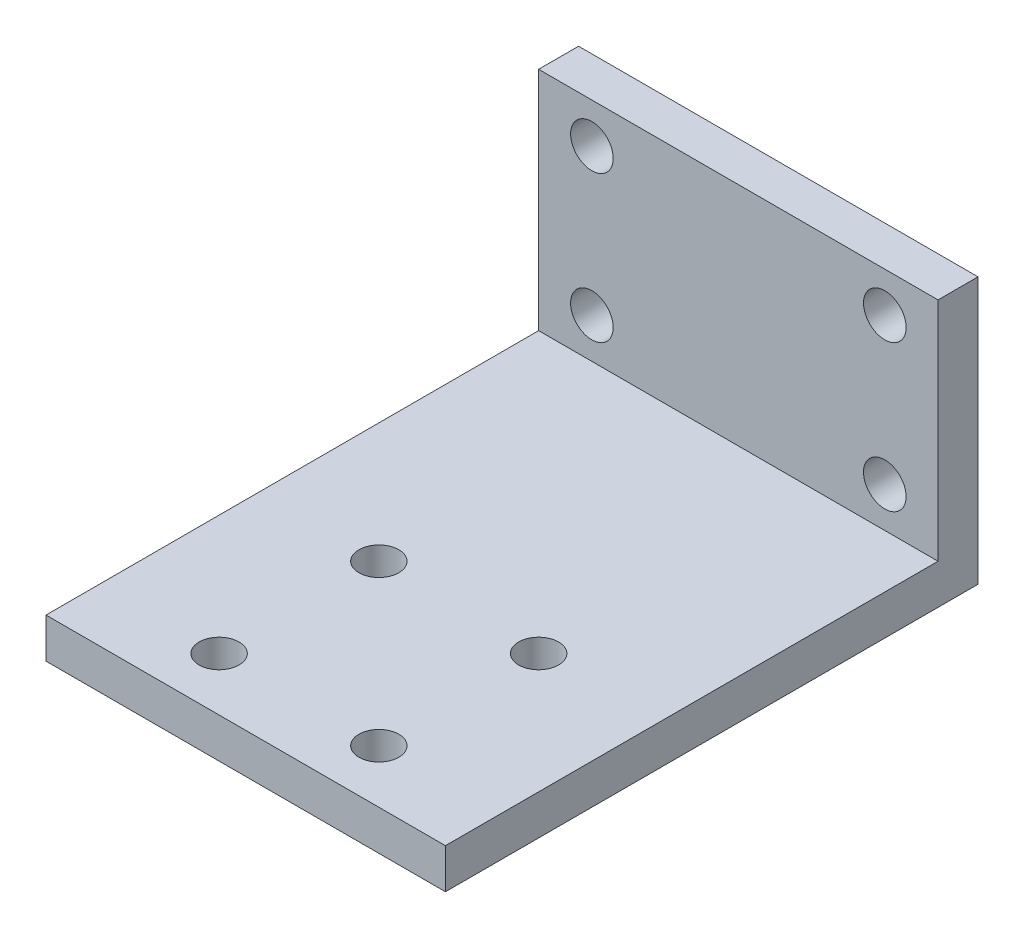
SolidWorks part; units mm, degrees
ref_plane "前视基准面" through (0, 0, 0) normal (0, 0, 1) x (1, 0, 0)
ref_plane "上视基准面" through (0, 0, 0) normal (0, 1, 0) x (1, 0, 0)
ref_plane "右视基准面" through (0, 0, 0) normal (1, 0, 0) x (0, 0, -1)
sketch "草图1" plane through (0, 0, 0) normal (0, 1, 0) x (1, 0, 0)
  line L1 (-21.3353, 6.9139) -> (8.6647, 6.9139)
  line L2 (-21.3353, 6.9139) -> (-21.3353, -33.0861)
  line L3 (-21.3353, -33.0861) -> (8.6647, -33.0861)
  line L4 (8.6647, 6.9139) -> (8.6647, -33.0861)
  dimension "D1" = 30
  dimension "D2" = 40
extrude "凸台-拉伸1" add sketch "草图1" along normal blind 3
sketch "草图2" plane through (0, 3, 0) normal (0, 1, 0) x (1, 0, 0)
  line L0 (8.6647, -33.0861) -> (8.6647, 6.9139) construction
  line L1 (-21.3353, 6.9139) -> (8.6647, 6.9139)
  line L2 (-21.3353, 6.9139) -> (-21.3353, 3.9139)
  line L3 (-21.3353, 3.9139) -> (8.6647, 3.9139)
  line L4 (8.6647, 6.9139) -> (8.6647, 3.9139)
  dimension "D1" = 3
extrude "凸台-拉伸2" add sketch "草图2" along normal blind 17
sketch "草图3" plane through (0, 0, -3.9139) normal (0, 0, 1) x (1, 0, 0)
  line L0 (-21.3353, 20) -> (-21.3353, 3) construction
  line L1 (8.6647, 20) -> (8.6647, 3) construction
  line L2 (-21.3353, 3) -> (8.6647, 3) construction
  line L3 (-21.3353, 20) -> (8.6647, 20) construction
  circle A0 centre (-17.3353, 17) radius 1.6
  circle A1 centre (4.6647, 17) radius 1.6
  circle A2 centre (-17.3353, 6) radius 1.6
  circle A3 centre (4.6647, 6) radius 1.6
  dimension "D1" = 3.2
  dimension "D2" = 3.2
  dimension "D3" = 3.2
  dimension "D4" = 3.2
  dimension "D5" = 4
  dimension "D6" = 4
  dimension "D7" = 4
  dimension "D8" = 4
  dimension "D9" = 3
  dimension "D10" = 3
  dimension "D11" = 3
  dimension "D12" = 3
extrude "切除-拉伸1" cut sketch "草图3" against normal blind 17
sketch "草图4" plane through (0, 0, 0) normal (0, -1, 0) x (1, 0, 0)
  line L0 (-21.3353, -6.9139) -> (-21.3353, 33.0861) construction
  circle A0 centre (-0.3353, 17.0861) radius 1.5
  circle A1 centre (-0.3353, 29.0861) radius 1.5
  circle A2 centre (-12.3353, 29.0861) radius 1.5
  circle A3 centre (-12.3353, 17.0861) radius 1.5
  dimension "D1" = 3
  dimension "D2" = 3
  dimension "D3" = 9
  dimension "D4" = 9
extrude "切除-拉伸2" cut sketch "草图4" against normal blind 10
